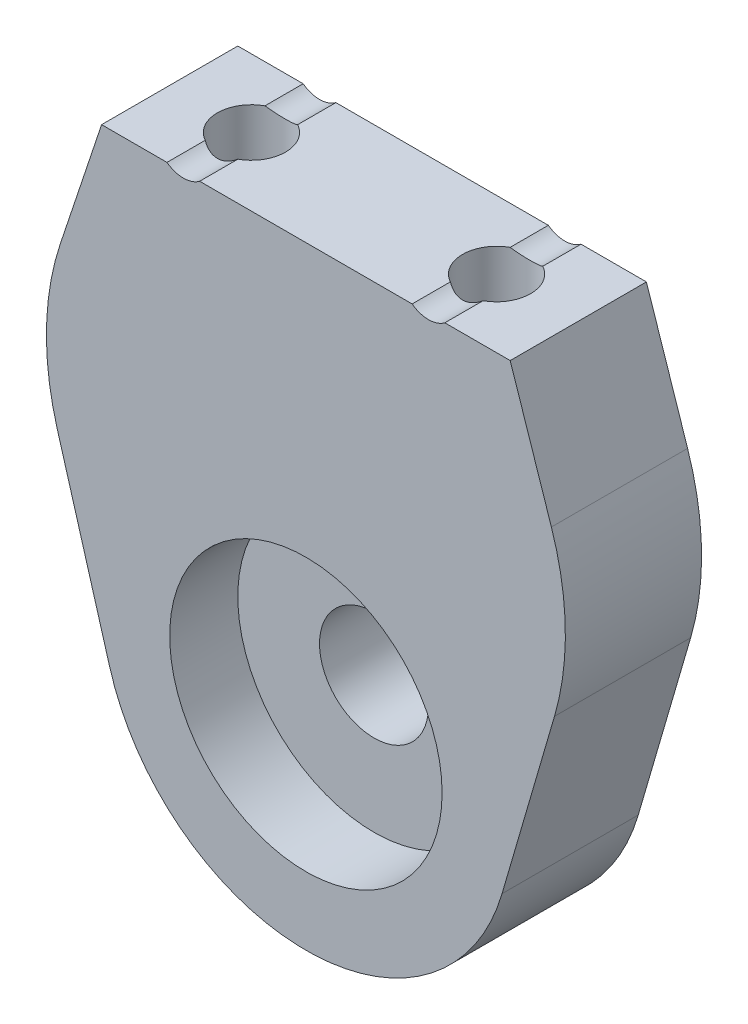
SolidWorks part; units mm, degrees
material "A2017"
ref_plane "正面" through (0, 0, 0) normal (0, 0, 1) x (1, 0, 0)
ref_plane "平面" through (0, 0, 0) normal (0, 1, 0) x (1, 0, 0)
ref_plane "右側面" through (0, 0, 0) normal (1, 0, 0) x (0, 0, -1)
sketch "ｽｹｯﾁ1" plane through (0, 0, 0) normal (0, 0, 1) x (1, 0, 0)
  circle A0 centre (0, 0) radius 7.5
  circle A1 centre (0, 0) radius 2
  dimension "D1" = 4
  dimension "D2" = 15
extrude "ﾎﾞｽ - 押し出し1" add sketch "ｽｹｯﾁ1" along normal blind 5
sketch "ｽｹｯﾁ2" plane through (0, 0, 5) normal (0, 0, 1) x (1, 0, 0)
  line L0 (0, 0) -> (0, 15) construction
  line L1 (-7.5, 0) -> (-7.5, 15)
  line L2 (-7.5, 15) -> (7.5, 15)
  line L3 (7.5, 15) -> (7.5, 0)
  circle A0 centre (0, 0) radius 7.5 construction
  arc A1 (-7.5, 0) -> (7.5, 0) centre (0, 0) cw
  dimension "D1" = 15
extrude "ﾎﾞｽ - 押し出し2" add sketch "ｽｹｯﾁ2" against normal up to surface (5 mm away) up to face at (7.5, 0, 0)
sketch "ｽｹｯﾁ3" plane through (0, 15, 0) normal (0, 1, 0) x (1, 0, 0)
  line L0 (-7.5, -2.5) -> (7.5, -2.5) construction
  line L3 (-7.5, 0) -> (-7.5, -5) construction
  line L4 (7.5, 0) -> (7.5, -5) construction
  line L5 (0, 0) -> (0, -5) construction
  line L6 (-7.5, 0) -> (7.5, 0) construction
  line L7 (7.5, -5) -> (-7.5, -5) construction
  circle A0 centre (-4.5, -2.5) radius 1
  circle A1 centre (4.5, -2.5) radius 1
  dimension "D1" = 3
  dimension "D2" = 2
extrude "ｶｯﾄ - 押し出し1" cut sketch "ｽｹｯﾁ3" against normal blind 5
sketch "ｽｹｯﾁ4" plane through (0, 0, 5) normal (0, 0, 1) x (1, 0, 0)
  line L0 (0, 0) -> (0, 15) construction
  line L1 (7.5, 15) -> (-7.5, 15) construction
  line L2 (0, 7.5) -> (-10, 7.5) construction
  line L3 (-10, 7.5) -> (-7.5, 15) construction
  line L4 (-10, 7.5) -> (-7.2, -2.1) construction
  line L5 (-7.5, 15) -> (-10, 7.5)
  line L6 (-10, 7.5) -> (-7.2, -2.1)
  line L7 (-7.5, 0) -> (-7.5, 15)
  line L8 (10, 7.5) -> (7.2, -2.1) construction
  line L9 (10, 7.5) -> (7.5, 15) construction
  line L10 (7.5, 0) -> (7.5, 15)
  line L11 (10, 7.5) -> (7.2, -2.1)
  line L12 (7.5, 15) -> (10, 7.5)
  arc A0 (-7.5, 0) -> (7.5, 0) centre (0, 0) ccw construction
  arc A1 (-7.2, -2.1) -> (-7.5, 0) centre (0, 0) cw
  arc A2 (7.2, -2.1) -> (7.5, 0) centre (0, 0) ccw
  dimension "D1" = 10
extrude "ﾎﾞｽ - 押し出し3" add sketch "ｽｹｯﾁ4" against normal up to surface (5 mm away) up to face at (0, 5.625, 0)
fillet "ﾌｨﾚｯﾄ1" radius 10 2 edges at (10, 7.5, 2.5) (-10, 7.5, 2.5)
sketch "ｽｹｯﾁ5" plane through (0, 0, 5) normal (0, 0, 1) x (1, 0, 0)
  line L0 (0, 0) -> (0, 12) construction
  line L1 (0, 12) -> (-8.1875, 12) construction
  line L2 (-9.1253, 4.5012) -> (-7.2, -2.1) construction
  line L3 (-8.1875, 15) -> (8.1875, 15)
  line L4 (9.0122, 10.4635) -> (7.5, 15) construction
  line L5 (7.5, 15) -> (-7.5, 15) construction
  line L6 (-7.5, 15) -> (-9.0122, 10.4635) construction
  line L7 (9.0122, 10.4635) -> (7.5, 15)
  line L8 (7.5, 15) -> (-7.5, 15)
  line L9 (-7.5, 15) -> (-9.0122, 10.4635)
  arc A0 (-8.1875, 15) -> (-6.4921, 14.475) centre (-8.1875, 12) ccw
  arc A1 (8.1875, 15) -> (6.4921, 14.475) centre (8.1875, 12) cw
  arc A2 (9.1253, 4.5012) -> (9.0122, 10.4635) centre (-0.4747, 7.3012) ccw construction
  arc A3 (-9.0122, 10.4635) -> (-9.1253, 4.5012) centre (0.4747, 7.3012) ccw construction
  arc A4 (6.4921, 14.475) -> (9.0122, 10.4635) centre (-0.4747, 7.3012) ccw
  arc A5 (-9.0122, 10.4635) -> (-6.4921, 14.475) centre (0.4747, 7.3012) ccw
  dimension "D2" = 6
  dimension "D1" = 12
extrude "ｶｯﾄ - 押し出し2" [suppressed] cut sketch "ｽｹｯﾁ5" against normal through all
sketch "ｽｹｯﾁ6" [suppressed] plane through (0, 0, 5) normal (0, 0, 1) x (1, 0, 0)
  arc A0 (9.8123, 12.4863) -> (6.852, 15) centre (6.852, 12) ccw construction
  arc A1 (-6.852, 15) -> (-9.8123, 12.4863) centre (-6.852, 12) ccw construction
  circle A2 centre (6.852, 12) radius 3
  circle A3 centre (-6.852, 12) radius 3
extrude "ﾎﾞｽ - 押し出し4" [suppressed] add sketch "ｽｹｯﾁ6" against normal up to surface (5 mm away) up to face at (0, 6.2933, 0)
sketch "ｽｹｯﾁ7" [suppressed] plane through (0, 0, 5) normal (0, 0, 1) x (1, 0, 0)
  circle A0 centre (6.852, 12) radius 1.5
  circle A1 centre (-6.852, 12) radius 1.5
  dimension "D1" = 3
  dimension "D2" = 3
extrude "ｶｯﾄ - 押し出し3" [suppressed] cut sketch "ｽｹｯﾁ7" against normal through all
sketch "ｽｹｯﾁ8" [suppressed] plane through (0, 0, 5) normal (0, 0, 1) x (1, 0, 0)
  line L0 (-6.852, 15) -> (-9.852, 15)
  line L1 (-9.852, 15) -> (-9.852, 11.7185)
  line L2 (-9.852, 11.7185) -> (-9.7997, 11.4419)
  line L3 (0, 0) -> (0, 15) construction
  line L4 (-6.852, 15) -> (6.852, 15) construction
  line L5 (9.852, 11.7185) -> (9.7997, 11.4419)
  line L6 (9.852, 15) -> (9.852, 11.7185)
  line L7 (6.852, 15) -> (9.852, 15)
  arc A0 (-7.3691, -1.3953) -> (7.3691, -1.3953) centre (0, 0) ccw construction
  arc A1 (-6.852, 15) -> (-9.7269, 11.1426) centre (-6.852, 12) ccw construction
  arc A2 (-6.852, 15) -> (-9.7997, 11.4419) centre (-6.852, 12) ccw
  arc A3 (6.852, 15) -> (9.7997, 11.4419) centre (6.852, 12) cw
extrude "ﾎﾞｽ - 押し出し5" [suppressed] add sketch "ｽｹｯﾁ8" against normal up to surface (5 mm away) up to face at (0, 6.2933, 0)
sketch "ｽｹｯﾁ10" [suppressed] plane through (0, 0, 0) normal (0, 0, -1) x (-1, 0, 0)
  line L0 (0, 15) -> (0, 0) construction
  line L1 (9.852, 15) -> (-9.852, 15) construction
sketch "ｽｹｯﾁ11" plane through (0, 0, 5) normal (0, 0, 1) x (1, 0, 0)
  circle A0 centre (0, 0) radius 5
  dimension "D1" = 10
extrude "ｶｯﾄ - 押し出し4" cut sketch "ｽｹｯﾁ11" against normal blind 2.5
sketch "ｽｹｯﾁ12" plane through (0, 0, 0) normal (0, 0, -1) x (-1, 0, 0)
  line L0 (-4.5, 10) -> (-4.5, 15.8) construction
  line L1 (-3.5, 10) -> (-5.5, 10) construction
  line L2 (7.5, 15) -> (-7.5, 15) construction
  line L3 (0, 0) -> (0, 15) construction
  circle A0 centre (-4.5, 15.8) radius 1
  circle A1 centre (4.5, 15.8) radius 1
  dimension "D1" = 2
  dimension "D2" = 0.8
extrude "ｶｯﾄ - 押し出し5" cut sketch "ｽｹｯﾁ12" against normal through all
hole_wizard "M3 ねじ穴1" positions "ｽｹｯﾁ13" profile "ｽｹｯﾁ14" tap size "M3" standard "JIS"
sketch "ｽｹｯﾁ13" plane through (0, 15, 0) normal (0, 1, 0) x (1, 0, 0)
  point P0 (-4.5, -2.5)
  point P3 (4.5, -2.5)
sketch "ｽｹｯﾁ14" plane through (-4.5, 15, 2.5) normal (1, 0, 0) x (0, 0, 1)
  line L0 (0, 0) -> (0, 9.2511)
  line L1 (0, 9.2511) -> (1.25, 8.5)
  line L2 (1.25, 8.5) -> (1.25, 0)
  line L5 (1.25, 0) -> (0, 0)
  line L10 (0, 9.2511) -> (-1.25, 8.5) construction
  line L11 (0, -6.35) -> (0, 107.95) construction
  dimension "ねじ下穴ﾄﾞﾘﾙ直径" = 2.5
  dimension "ねじ下穴ﾄﾞﾘﾙの深さ" = 8.5
  dimension "ﾄﾞﾘﾙ角度" = 118
cosmetic thread "穴のねじ山1" parameters "D1"=6, "D2"=3
cosmetic thread "穴のねじ山2" parameters "D1"=6, "D2"=3
